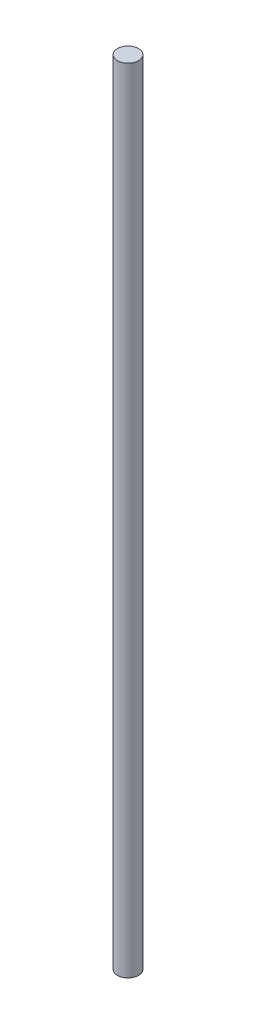
SolidWorks part; units mm, degrees
ref_plane "Front Plane" through (0, 0, 0) normal (0, 0, 1) x (1, 0, 0)
ref_plane "Top Plane" through (0, 0, 0) normal (0, 1, 0) x (1, 0, 0)
ref_plane "Right Plane" through (0, 0, 0) normal (1, 0, 0) x (0, 0, -1)
ref_axis "AxisX" through (88.99, 0, 0) along (-1, 0, 0)
ref_axis "AxisY" through (0, -55, 0) along (0, 1, 0)
ref_axis "AxisZ" through (0, 0, -88.99) along (0, 0, 1)
sketch "Sketch1" plane through (0, 0, 0) normal (0, 1, 0) x (1, 0, 0)
  circle A0 centre (-37.3526, 21.8091) radius 4
extrude "Boss-Extrude1" add sketch "Sketch1" along normal blind 300
equation "\"Weight In Water\"= round ( \"SW-Mass\" - \"SW-Volume\" * 0.000001025 , 1 )"
